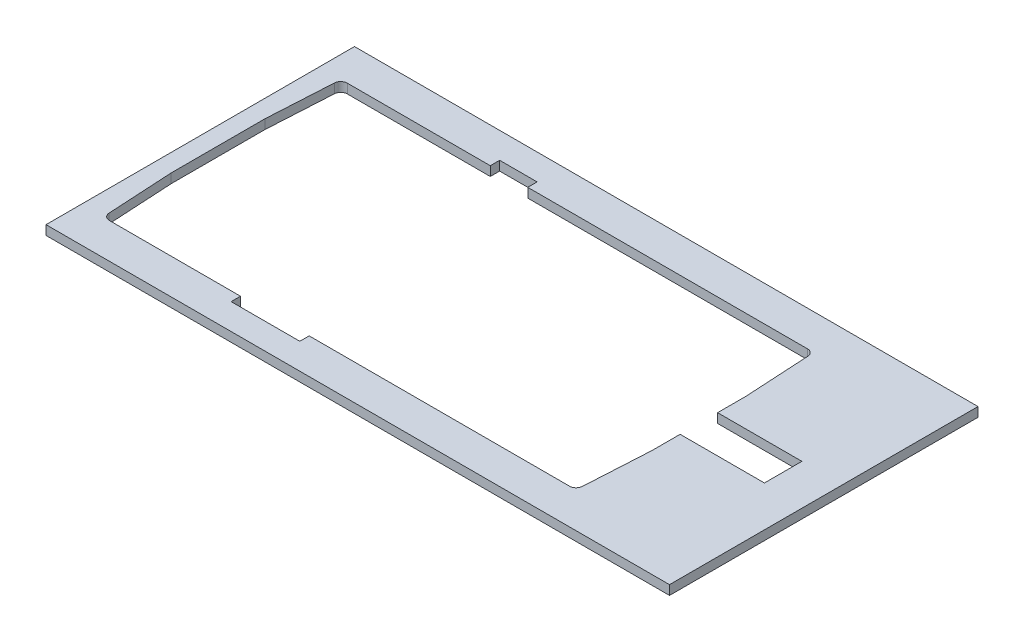
SolidWorks part; units mm, degrees
ref_plane "Front Plane" through (0, 0, 0) normal (0, 0, 1) x (1, 0, 0)
ref_plane "Top Plane" through (0, 0, 0) normal (0, 1, 0) x (1, 0, 0)
ref_plane "Right Plane" through (0, 0, 0) normal (1, 0, 0) x (0, 0, -1)
sketch "Sketch1" plane through (0, 0, 0) normal (0, 1, 0) x (1, 0, 0)
  line L0 (-41.1557, 15.8278) -> (4.6477, 15.8278)
  line L1 (-50.1423, 27.1278) -> (149.5477, 27.1278)
  line L2 (-50.1423, 27.1278) -> (-50.1423, -71.6722)
  line L3 (-50.1423, -71.6722) -> (149.5477, -71.6722)
  line L4 (149.5477, 27.1278) -> (149.5477, -71.6722)
  line L5 (109.5477, -7.2631) -> (109.5477, -16.2722)
  line L6 (109.5477, -16.2722) -> (136.5477, -16.2722)
  line L7 (136.5477, -16.2722) -> (136.5477, -28.2722)
  line L8 (136.5477, -28.2722) -> (109.5477, -28.2722)
  line L9 (109.5477, -28.2722) -> (109.5477, -37.2813)
  line L10 (106.2511, -60.3722) -> (22.8477, -60.3722)
  line L11 (-44.4523, -37.2813) -> (-44.4523, -7.2631)
  line L12 (4.6477, 15.8278) -> (4.6477, 18.8278)
  line L13 (4.6477, 18.8278) -> (16.6477, 18.8278)
  line L14 (16.6477, 18.8278) -> (16.6477, 15.8278)
  line L15 (16.6477, 15.8278) -> (106.2511, 15.8278)
  line L16 (0.8477, -60.3722) -> (0.8477, -63.3722)
  line L17 (0.8477, -63.3722) -> (22.8477, -63.3722)
  line L18 (22.8477, -63.3722) -> (22.8477, -60.3722)
  line L19 (0.8477, -60.3722) -> (-41.1557, -60.3722)
  line L20 (-43.2523, 13.847) -> (-44.4523, -7.2631)
  line L21 (-44.4523, -37.2813) -> (-43.2523, -58.3914)
  line L22 (108.3477, 13.847) -> (109.5477, -7.2631)
  line L23 (109.5477, -37.2813) -> (108.3477, -58.3914)
  arc A0 (-41.1557, 15.8278) -> (-43.2523, 13.847) centre (-41.1557, 13.7278) ccw
  arc A1 (-43.2523, -58.3914) -> (-41.1557, -60.3722) centre (-41.1557, -58.2722) ccw
  arc A2 (108.3477, 13.847) -> (106.2511, 15.8278) centre (106.2511, 13.7278) ccw
  arc A3 (106.2511, -60.3722) -> (108.3477, -58.3914) centre (106.2511, -58.2722) ccw
  point P25 (136.5477, -22.2722)
  point P28 (-44.4523, -22.2722)
  point P33 (0, 0)
  dimension "D3" = 2.1
  dimension "D5" = 2.1
  dimension "D21" = 4.2
  dimension "D23" = 4.2
  dimension "D1" = 199.69
  dimension "D2" = 98.8
  dimension "D6" = 12
  dimension "D7" = 27
  dimension "D9" = 40
  dimension "D10" = 3
  dimension "D11" = 12
  dimension "D13" = 3
  dimension "D14" = 22
  dimension "D4" = 11.3
  dimension "D12" = 1.2
  dimension "D15" = 1.2
  dimension "D16" = 23.0909
  dimension "D17" = 23.0909
  dimension "D19" = 154
  dimension "D8" = 1.2
  dimension "D20" = 23.0909
  dimension "D22" = 76.2
  dimension "D24" = 1.2
  dimension "D25" = 23.0909
  dimension "D26" = 38.1
  dimension "D27" = 45.3
  dimension "D18" = 49.1
extrude "Boss-Extrude1" add sketch "Sketch1" along normal blind 3
equation "\"Fit\"= 1"
equation "\"cover width\"= 98.8"
equation "\"top phone insert length\"= 199.69"
equation "\"thinner acrylic\"= 3mm"
equation "\"D1@Sketch1\"=\"top phone insert length\""
equation "\"D2@Sketch1\"=\"cover width\""
equation "\"D1@Boss-Extrude1\"=\"thinner acrylic\""
equation "\"phone edge to bottom\"= 40"
equation "\"charge cable width\"= 12"
equation "\"charge cable length\"= 27"
equation "\"phone width\"= 76.2"
equation "\"phone length\"= 154"
equation "\"D6@Sketch1\"=\"charge cable width\""
equation "\"D7@Sketch1\"=\"charge cable length\""
equation "\"D9@Sketch1\"=\"phone edge to bottom\""
equation "\"button depth\"= 3"
equation "\"volume button length\"= 22"
equation "\"power button length\"= 12"
equation "\"power button from top\"= 49.1"
equation "\"volume button from top\"= 45.3"
equation "\"D10@Sketch1\"=\"button depth\""
equation "\"D11@Sketch1\"=\"power button length\""
equation "\"D13@Sketch1\"=\"button depth\""
equation "\"D14@Sketch1\"=\"volume button length\""
equation "\"D4@Sketch1\"=(\"cover width\"-\"phone width\")/2"
equation "\"corner radius\" = 2.1"
equation "\"D3@Sketch1\"=\"corner radius\""
equation "\"D5@Sketch1\"=\"corner radius\""
equation "\"edge bend\"= 1.2"
equation "\"D12@Sketch1\"=\"edge bend\""
equation "\"D15@Sketch1\"=\"edge bend\""
equation "\"D16@Sketch1\" = \"phone width\" / 3.3"
equation "\"D17@Sketch1\" = \"phone width\" / 3.3"
equation "\"D19@Sketch1\"=\"phone length\""
equation "\"D21@Sketch1\"=\"corner radius\"*2"
equation "\"D8@Sketch1\"=\"edge bend\""
equation "\"D20@Sketch1\" = \"phone width\" / 3.3"
equation "\"D22@Sketch1\"=\"phone width\""
equation "\"D23@Sketch1\"=\"corner radius\"*2"
equation "\"D24@Sketch1\"=\"edge bend\""
equation "\"D25@Sketch1\" = \"phone width\" / 3.3"
equation "\"D26@Sketch1\"=\"phone width\"/2"
equation "\"D27@Sketch1\"=\"volume button from top\""
equation "\"D18@Sketch1\"=\"power button from top\""
